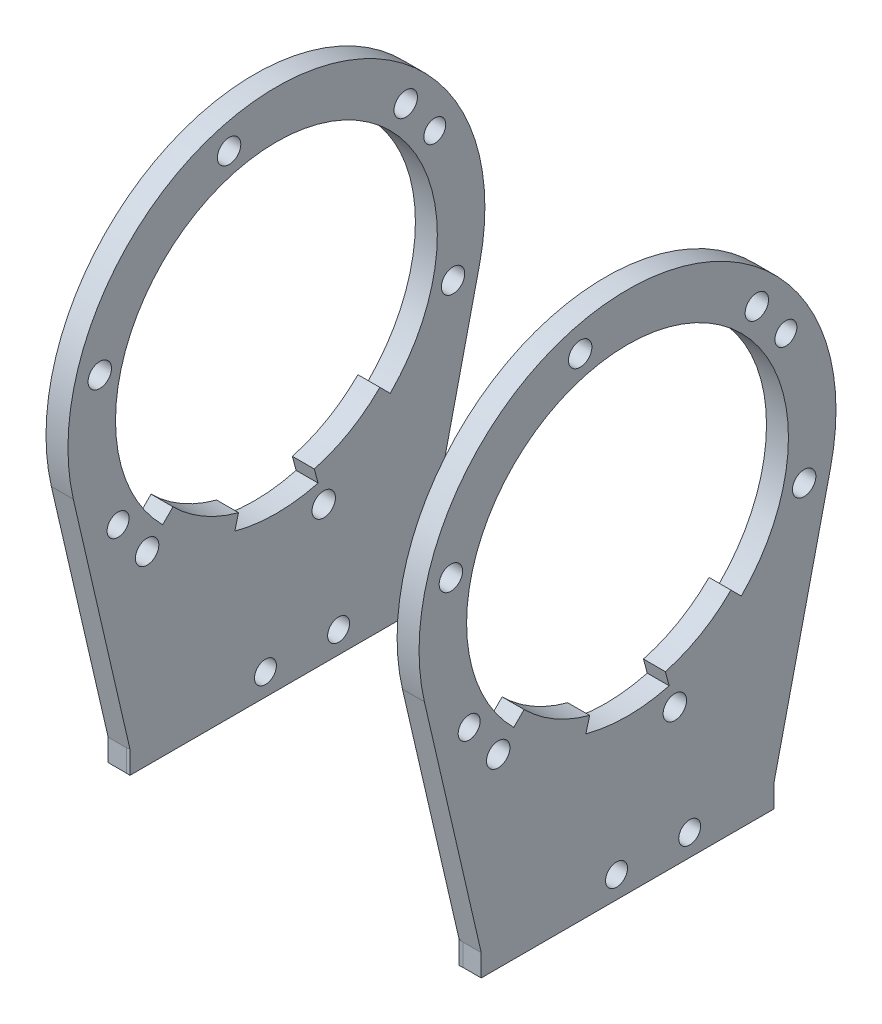
SolidWorks part; units mm, degrees
material "A-玻璃纤维"
ref_plane "前视基准面" through (0, 0, 0) normal (0, 0, 1) x (1, 0, 0)
ref_plane "上视基准面" through (0, 0, 0) normal (0, 1, 0) x (1, 0, 0)
ref_plane "右视基准面" through (0, 0, 0) normal (1, 0, 0) x (0, 0, -1)
other "Configuration Table"
sketch "草图1" plane through (0, 0, 0) normal (0, 1, 0) x (1, 0, 0)
  line L1 (-22.5, -20) -> (22.5, -20)
  line L2 (-22.5, -20) -> (-22.5, 20)
  line L3 (-22.5, 20) -> (22.5, 20)
  line L4 (22.5, -20) -> (22.5, 20)
  line L5 (-22.5, -20) -> (22.5, 20) construction
  line L6 (-22.5, 20) -> (22.5, -20) construction
  point P0 (0, 0)
  dimension "D1" = 40
  dimension "D2" = 45
extrude "凸台-拉伸1" add sketch "草图1" along normal blind 3
sketch "草图2" plane through (22.5, 0, 0) normal (1, 0, 0) x (0, 0, -1)
  line L0 (-27.7668, 36.5772) -> (-20, 3)
  line L2 (-20, 3) -> (-20, 0)
  line L3 (-20, 0) -> (20, 0)
  line L4 (20, 0) -> (20, 3)
  line L5 (20, 3) -> (27.7668, 36.5772)
  circle A0 centre (0, 43) radius 28.5
  line M4 (-20, 0) -> (20, 0)
  line M5 (20, 0) -> (20, 3)
  line M6 (20, 3) -> (-20, 3)
  line M7 (-20, 3) -> (-20, 0)
  dimension "D1" = 57
  dimension "D2" = 43
extrude "凸台-拉伸2" add sketch "草图2" along normal blind 3 contours A0 | A0 L0 L5 M6 | M7 M4 M5 M6 region at (22.5, 11.8893, 0) region at (22.5, 43, 0) region at (22.5, 1.5, 0)
extrude "凸台-拉伸3" add sketch "草图2<4>" against normal blind 3 from surface contours A0 | A0 L0 L5 M6 | M7 M4 M5 M6 region at (22.5, 11.8893, 0) region at (22.5, 43, 0) region at (22.5, 1.5, 0) starting at face at (-22.5, 1.5, 0)
sketch "草图2<4>" plane through (22.5, 0, 0) normal (1, 0, 0) x (0, 0, -1) same geometry as "草图2"
sketch "草图3" plane through (25.5, 0, 0) normal (1, 0, 0) x (0, 0, -1)
  line L0 (0, 43) -> (17.6777, 60.6777) construction
  line L1 (0, 43) -> (25, 43) construction
  circle A0 centre (0, 43) radius 22
  circle A1 centre (0, 43) radius 25 construction
  circle A2 centre (17.6777, 60.6777) radius 1.6
  circle A3 centre (24.1481, 36.5295) radius 1.6
  circle A4 centre (6.4705, 18.8519) radius 1.6
  circle A5 centre (-17.6777, 25.3223) radius 1.6
  circle A6 centre (-24.1481, 49.4705) radius 1.6
  circle A7 centre (-6.4705, 67.1481) radius 1.6
  dimension "D1" = 44
  dimension "D2" = 50
  dimension "D3" = 3.2
  dimension "D5" = 45
  dimension "D4" = 6
extrude "切除-拉伸1" cut sketch "草图3" against normal through all
sketch "草图4" plane through (25.5, 0, 0) normal (1, 0, 0) x (0, 0, -1)
  line L0 (-15.5563, 27.4437) -> (0, 43)
  line L1 (0, 43) -> (15.5563, 27.4437)
  line L2 (0, 21) -> (0, 43)
  line L3 (-5.694, 21.7496) -> (0, 43)
  line L4 (5.694, 21.7496) -> (0, 43)
  circle A0 centre (0, 43) radius 20
  circle A1 centre (0, 43) radius 22 construction
  circle A2 centre (0, 43) radius 22
  circle M4 centre (0, 43) radius 22
  dimension "D1" = 40
  dimension "D2" = 45
  dimension "D3" = 45
  dimension "D4" = 15
  dimension "D5" = 15
extrude "凸台-拉伸4" add sketch "草图4" against normal blind 3 contours A0 L0 L3 M4 | A0 L4 L1 M4 region at (25.5, 25.0069, 10.3883) region at (25.5, 25.0069, -10.3883)
extrude "凸台-拉伸5" add sketch "草图4<3>" against normal blind 3 from surface contours A0 L0 L3 M4 | A0 L4 L1 M4 region at (25.5, 25.0069, 10.3883) region at (25.5, 25.0069, -10.3883) starting at face at (-22.5, 60.6777, -19.2777)
sketch "草图4<3>" plane through (25.5, 0, 0) normal (1, 0, 0) x (0, 0, -1) same geometry as "草图4"
sketch "草图7" plane through (25.5, 0, 0) normal (1, 0, 0) x (0, 0, -1)
  line L0 (-25, 43) -> (25, 43) construction
  line L1 (21.6506, 55.5) -> (-21.6506, 30.5) construction
  circle A0 centre (0, 43) radius 25 construction
  circle A1 centre (21.6506, 55.5) radius 1.5
  circle A2 centre (-21.6506, 30.5) radius 1.5
  dimension "D1" = 50
  dimension "D3" = 3
  dimension "D4" = 3
  dimension "D2" = 30
extrude "切除-拉伸3" cut sketch "草图7" against normal through all
sketch "草图10" plane through (0, 3, 0) normal (0, 1, 0) x (1, 0, 0)
  line L1 (-20, -30) -> (20, -30)
  line L2 (-20, -30) -> (-20, 30)
  line L3 (-20, 30) -> (20, 30)
  line L4 (20, -30) -> (20, 30)
  line L5 (-20, -30) -> (20, 30) construction
  line L6 (-20, 30) -> (20, -30) construction
  point P0 (0, 0)
  dimension "D1" = 60
  dimension "D2" = 40
extrude "凸台-拉伸6" add sketch "草图10" against normal blind 3
sketch "草图8" plane through (0, 3, 0) normal (0, 1, 0) x (1, 0, 0)
  line L1 (-8.6718, -15.02) -> (8.6718, -15.02)
  line L2 (8.6718, -15.02) -> (17.3436, 0)
  line L3 (17.3436, 0) -> (8.6718, 15.02)
  line L4 (8.6718, 15.02) -> (-8.6718, 15.02)
  line L5 (-8.6718, 15.02) -> (-17.3436, 0)
  line L6 (-17.3436, 0) -> (-8.6718, -15.02)
  circle A0 centre (0, 0) radius 15.02
  dimension "D1" = 30.04
extrude "切除-拉伸4" cut sketch "草图8" against normal through all contours A0 region at (0, 3, 0)
sketch "草图15" plane through (0, 3, 0) normal (0, 1, 0) x (1, 0, 0)
  line L0 (20, 30) -> (-20, 30) construction
  line L1 (-20, 30) -> (-20, 20) construction
  line L2 (-15, 25) -> (15, 25) construction
  line L3 (-15, 25) -> (-15, -25) construction
  line L4 (20, 20) -> (20, 30) construction
  line L5 (-20, -30) -> (20, -30) construction
  circle A0 centre (-15, 25) radius 2.1
  circle A1 centre (15, 25) radius 2.1
  circle A2 centre (15, -25) radius 2.1
  circle A3 centre (-15, -25) radius 2.1
  dimension "D1" = 4.2
  dimension "D2" = 5
  dimension "D3" = 5
  dimension "D7" = 5
  dimension "D8" = 5
  dimension "D6" = 90
  dimension "D4" = 2
  dimension "D5" = 2
extrude "切除-拉伸5" cut sketch "草图15" against normal through all
fillet "圆角1" radius 3 8 edges at (-20, 1.5, 30) (-20, 1.5, 20) (20, 1.5, 30) (20, 1.5, 20) (20, 1.5, -30) (20, 1.5, -20) (-20, 1.5, -20) (-20, 1.5, -30)
sketch "草图16" plane through (0, 3, 0) normal (0, 1, 0) x (1, 0, 0)
  line L1 (-22.5, -30) -> (22.5, -30)
  line L2 (-22.5, -30) -> (-22.5, 30)
  line L3 (-22.5, 30) -> (22.5, 30)
  line L4 (22.5, -30) -> (22.5, 30)
  line L5 (-22.5, -30) -> (22.5, 30) construction
  line L6 (-22.5, 30) -> (22.5, -30) construction
  point P0 (0, 0)
extrude "切除-拉伸6" cut sketch "草图16" against normal blind 10
sketch "草图17" plane through (-25.5, 0, 0) normal (-1, 0, 0) x (0, 0, 1)
  line L0 (-20, 0) -> (-20, 3) construction
  line L1 (20, 0) -> (-20, 0) construction
  line L2 (-8.5, 3) -> (1.5, 3) construction
  circle A0 centre (-8.5, 3) radius 1.5
  circle A1 centre (1.5, 3) radius 1.5
  dimension "D1" = 3
  dimension "D2" = 11.5
  dimension "D3" = 3
  dimension "D5" = 10
  dimension "D4" = 2
extrude "切除-拉伸7" cut sketch "草图17" against normal through all
